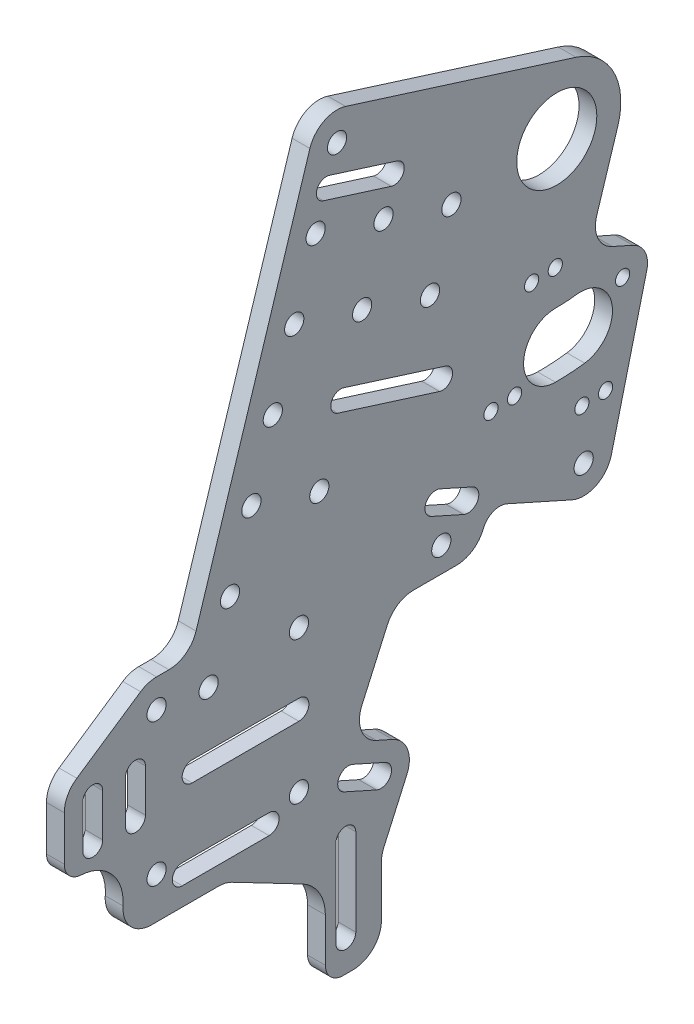
SolidWorks part; units mm, degrees
material "5052-H32"
ref_plane "Front Plane" through (0, 0, 0) normal (0, 0, 1) x (1, 0, 0)
ref_plane "Top Plane" through (0, 0, 0) normal (0, 1, 0) x (1, 0, 0)
ref_plane "Right Plane" through (0, 0, 0) normal (1, 0, 0) x (0, 0, -1)
sketch "Sketch2" plane through (0, 0, 0) normal (1, 0, 0) x (0, 0, -1)
  line L3 (55, 0) -> (-55, 0) construction
  line L9 (71.6952, 111.2048) -> (68.2175, 112.7608) construction
  line L28 (0, 0) -> (-57.2178, 40.0643) construction
  line L40 (0, 0) -> (113.3671, 198.5091) construction
  line L41 (113.3671, 198.5091) -> (58.7631, 215.7257) construction
  line L42 (99.338, 182.3162) -> (24.13, 14.224) construction
  line L44 (30.078, 221.0415) -> (54.3024, 213.4035)
  line L45 (32.2166, 227.8243) -> (56.441, 220.1864)
  line L49 (104.399, 158.5001) -> (136.8581, 143.9772) construction
  line L50 (136.8581, 143.9772) -> (122.3352, 111.518) construction
  line L51 (112.8406, 159.0638) -> (145.2997, 144.5408) construction
  line L56 (43.9148, 180.4584) -> (36.2769, 156.2339) construction
  line L57 (-29.4365, 93.5262) -> (-29.4365, 42.7262) construction
  line L61 (122.3352, 111.518) -> (89.876, 126.041) construction
  line L62 (89.876, 126.041) -> (104.399, 158.5001) construction
  line L63 (104.399, 158.5001) -> (122.3352, 111.518) construction
  line L65 (145.2997, 144.5408) -> (130.7768, 112.0817) construction
  line L66 (130.7768, 112.0817) -> (98.3176, 126.6046) construction
  line L67 (98.3176, 126.6046) -> (112.8406, 159.0638) construction
  line L68 (112.8406, 159.0638) -> (130.7768, 112.0817) construction
  line L69 (58.7631, 215.7257) -> (31.1473, 224.4329) construction
  line L70 (40.5747, 41.6494) -> (37.0969, 43.2054) construction
  line L71 (38.1, 20.2565) -> (38.1, -10.7315) construction
  line L72 (41.656, 20.2565) -> (41.656, -10.7315)
  line L73 (34.544, 20.2565) -> (34.544, -10.7315)
  line L74 (0, -14.2875) -> (38.1, -14.2875) construction
  line L75 (-20.2565, 38.1) -> (10.7315, 38.1) construction
  line L76 (-20.2565, 41.656) -> (10.7315, 41.656)
  line L77 (-20.2565, 34.544) -> (10.7315, 34.544)
  line L78 (14.2875, 38.1) -> (14.2875, 0) construction
  line L79 (-52.2013, 78.1643) -> (-52.2013, 62.9243) construction
  line L80 (-48.6453, 78.1643) -> (-48.6453, 62.9243)
  line L81 (-55.7573, 78.1643) -> (-55.7573, 62.9243)
  line L82 (-36.9613, 78.1643) -> (-36.9613, 62.9243) construction
  line L83 (-33.4053, 78.1643) -> (-33.4053, 62.9243)
  line L84 (-40.5173, 78.1643) -> (-40.5173, 62.9243)
  line L85 (31.1473, 224.4329) -> (-10.8613, 91.1986) construction
  line L86 (31.1473, 224.4329) -> (34.9663, 236.5451) construction
  line L92 (27.3284, 212.3207) -> (75.7772, 197.0448) construction
  line L93 (19.6904, 188.0963) -> (68.1392, 172.8204) construction
  line L94 (36.2769, 156.2339) -> (12.0525, 163.8719) construction
  line L95 (36.2769, 156.2339) -> (72.6135, 144.777) construction
  line L96 (37.3462, 159.6254) -> (73.6828, 148.1685)
  line L97 (35.2076, 152.8425) -> (71.5442, 141.3856)
  line L98 (36.2769, 156.2339) -> (28.639, 132.0095) construction
  line L99 (28.639, 132.0095) -> (4.4146, 139.6475) construction
  line L100 (-29.4365, 68.1262) -> (-16.7365, 68.1262) construction
  line L101 (-16.7365, 68.1262) -> (21.3635, 68.1262) construction
  line L102 (-16.7365, 71.6822) -> (21.3635, 71.6822)
  line L103 (-16.7365, 64.5702) -> (21.3635, 64.5702)
  line L104 (38.0214, 246.2349) -> (120.2412, 220.3111)
  line L105 (25.2765, 239.6003) -> (-15.3369, 110.7911)
  line L106 (-29.4365, 103.6862) -> (-25.0266, 103.6862)
  line L107 (-35.1197, 101.9481) -> (-57.8844, 86.5862)
  line L108 (-62.3613, 62.2565) -> (-62.3613, 78.1643)
  line L109 (-31.257, 27.94) -> (-7.2528, 27.94)
  line L110 (30.7975, -15.5575) -> (30.7975, 0)
  line L113 (135.1691, 191.635) -> (127.6222, 167.6992)
  line L114 (133.1625, 155.37) -> (140.4889, 152.092)
  line L115 (145.4838, 141.8254) -> (132.8214, 91.067)
  line L116 (118.8141, 84.2522) -> (95.6442, 94.6189)
  line L117 (50.8, 6.3603) -> (50.8, -11.7475)
  line L118 (37.1475, -21.9075) -> (40.64, -21.9075)
  line L120 (54.7606, 42.2589) -> (48.9643, 44.8523)
  line L121 (52.9447, 78.6256) -> (43.8397, 58.2757)
  line L122 (59.8853, 28.8354) -> (51.6859, 10.5098)
  line L123 (62.2187, 84.6362) -> (77.6364, 84.6362)
  line L124 (87.2546, 91.416) -> (86.9104, 90.6468)
  line L125 (30.7975, 0) -> (15.3035, 0) construction
  line L126 (22.4684, 13.7378) -> (-2.5545, 26.7884)
  line L127 (0, 0) -> (0, 15.494) construction
  line L128 (39.0186, 38.1716) -> (50.6112, 32.9849) construction
  line L129 (70.1392, 107.727) -> (81.7318, 102.5402) construction
  line L131 (71.6952, 111.2048) -> (83.2878, 106.018)
  line L132 (68.5832, 104.2492) -> (80.1757, 99.0625)
  line L133 (40.5747, 41.6494) -> (52.1672, 36.4626)
  line L134 (37.4626, 34.6938) -> (49.0552, 29.5071)
  circle A36 centre (0, 0) radius 14.2875 construction
  circle A37 centre (-57.2178, 40.0643) radius 14.2875 construction
  circle A38 centre (113.3671, 198.5091) radius 14.2875
  arc A39 (54.3024, 213.4035) -> (56.441, 220.1864) centre (55.3717, 216.795) ccw
  arc A40 (32.2166, 227.8243) -> (30.078, 221.0415) centre (31.1473, 224.4329) ccw
  circle A49 centre (-29.4365, 42.7262) radius 3.429
  circle A50 centre (21.3635, 93.5262) radius 3.429
  circle A51 centre (122.9635, 93.5262) radius 3.429
  circle A54 centre (104.399, 158.5001) radius 2.54
  circle A55 centre (136.8581, 143.9772) radius 2.54
  circle A56 centre (122.3352, 111.518) radius 2.54
  circle A57 centre (89.876, 126.041) radius 2.54
  arc A60 (113.3671, 135.0091) -> (121.8087, 135.5727) centre (113.3671, 198.5091) ccw construction
  circle A61 centre (112.8406, 159.0638) radius 2.54
  circle A62 centre (130.7768, 112.0817) radius 2.54
  circle A63 centre (98.3176, 126.6046) radius 2.54
  circle A64 centre (-29.4365, 93.5262) radius 3.429
  circle A65 centre (21.3635, 42.7262) radius 3.429
  circle A66 centre (72.1635, 93.5262) radius 3.429
  arc A67 (41.656, 20.2565) -> (34.544, 20.2565) centre (38.1, 20.2565) ccw
  arc A68 (34.544, -10.7315) -> (41.656, -10.7315) centre (38.1, -10.7315) ccw
  arc A69 (-20.2565, 41.656) -> (-20.2565, 34.544) centre (-20.2565, 38.1) ccw
  arc A70 (10.7315, 34.544) -> (10.7315, 41.656) centre (10.7315, 38.1) ccw
  arc A71 (-48.6453, 78.1643) -> (-55.7573, 78.1643) centre (-52.2013, 78.1643) ccw
  arc A72 (-55.7573, 62.9243) -> (-48.6453, 62.9243) centre (-52.2013, 62.9243) ccw
  arc A73 (-33.4053, 78.1643) -> (-40.5173, 78.1643) centre (-36.9613, 78.1643) ccw
  arc A74 (-40.5173, 62.9243) -> (-33.4053, 62.9243) centre (-36.9613, 62.9243) ccw
  circle A75 centre (34.9663, 236.5451) radius 3.429
  circle A76 centre (27.3284, 212.3207) radius 3.429
  circle A77 centre (19.6904, 188.0963) radius 3.429
  circle A78 centre (12.0525, 163.8719) radius 3.429
  circle A79 centre (4.4146, 139.6475) radius 3.429
  circle A80 centre (-3.2234, 115.423) radius 3.429
  circle A81 centre (-10.8613, 91.1986) radius 3.429
  circle A82 centre (51.5528, 204.6828) radius 3.429
  circle A83 centre (43.9148, 180.4584) radius 3.429
  circle A84 centre (75.7772, 197.0448) radius 3.429
  circle A85 centre (68.1392, 172.8204) radius 3.429
  arc A86 (37.3462, 159.6254) -> (35.2076, 152.8425) centre (36.2769, 156.2339) ccw
  arc A87 (71.5442, 141.3856) -> (73.6828, 148.1685) centre (72.6135, 144.777) ccw
  circle A88 centre (28.639, 132.0095) radius 3.429
  arc A89 (-16.7365, 71.6822) -> (-16.7365, 64.5702) centre (-16.7365, 68.1262) ccw
  arc A90 (21.3635, 64.5702) -> (21.3635, 71.6822) centre (21.3635, 68.1262) ccw
  arc A91 (38.0214, 246.2349) -> (25.2765, 239.6003) centre (34.9663, 236.5451) ccw
  arc A92 (120.2412, 220.3111) -> (135.1691, 191.635) centre (113.3671, 198.5091) cw
  arc A93 (-35.1197, 101.9481) -> (-29.4365, 103.6862) centre (-29.4365, 93.5262) cw
  arc A94 (-62.3613, 78.1643) -> (-57.8844, 86.5862) centre (-52.2013, 78.1643) cw
  arc A95 (-25.0266, 103.6862) -> (-15.3369, 110.7911) centre (-25.0266, 113.8462) ccw
  arc A96 (-56.356, 55.9159) -> (-62.3613, 62.2565) centre (-56.0113, 62.2565) cw
  arc A97 (-41.388, 38.8666) -> (-56.356, 55.9159) centre (-57.2178, 40.0643) ccw
  arc A99 (-31.257, 27.94) -> (-41.388, 38.8666) centre (-31.257, 38.1) cw
  arc A100 (37.1475, -21.9075) -> (30.7975, -15.5575) centre (37.1475, -15.5575) cw
  arc A101 (140.4889, 152.092) -> (145.4838, 141.8254) centre (136.8581, 143.9772) cw
  arc A102 (132.8214, 91.067) -> (118.8141, 84.2522) centre (122.9635, 93.5262) cw
  arc A105 (133.1625, 155.37) -> (127.6222, 167.6992) centre (137.3119, 164.644) cw
  arc A106 (121.8087, 135.5727) -> (112.9541, 135.0104) centre (113.3671, 198.5091) cw construction
  arc A107 (112.8797, 123.5807) -> (123.3282, 124.2442) centre (113.3671, 198.5091) ccw
  arc A108 (113.0284, 146.4402) -> (120.2892, 146.9013) centre (113.3671, 198.5091) ccw
  arc A109 (113.0284, 146.4402) -> (112.8797, 123.5807) centre (112.9541, 135.0104) ccw
  arc A110 (123.3282, 124.2442) -> (120.2892, 146.9013) centre (121.8087, 135.5727) ccw
  arc A111 (40.64, -21.9075) -> (50.8, -11.7475) centre (40.64, -11.7475) ccw
  arc A112 (50.8, 6.3603) -> (51.6859, 10.5098) centre (60.96, 6.3603) cw
  arc A113 (54.7606, 42.2589) -> (59.8853, 28.8354) centre (50.6112, 32.9849) cw
  arc A114 (48.9643, 44.8523) -> (43.8397, 58.2757) centre (53.1137, 54.1263) cw
  arc A115 (62.2187, 84.6362) -> (52.9447, 78.6256) centre (62.2187, 74.4762) ccw
  arc A117 (77.6364, 84.6362) -> (86.9104, 90.6468) centre (77.6364, 94.7962) ccw
  arc A118 (87.2546, 91.416) -> (95.6442, 94.6189) centre (93.0509, 88.8226) cw
  arc A121 (30.7975, 0) -> (22.4684, 13.7378) centre (15.3035, 0) ccw
  arc A122 (-7.2528, 27.94) -> (-2.5545, 26.7884) centre (-7.2528, 17.78) cw
  arc A126 (71.6952, 111.2048) -> (68.5832, 104.2492) centre (70.1392, 107.727) ccw
  arc A127 (80.1757, 99.0625) -> (83.2878, 106.018) centre (81.7318, 102.5402) ccw
  arc A128 (40.5747, 41.6494) -> (37.4626, 34.6938) centre (39.0186, 38.1716) ccw
  arc A129 (49.0552, 29.5071) -> (52.1672, 36.4626) centre (50.6112, 32.9849) ccw
  point P26 (66.6614, 109.283)
  point P31 (113.3671, 135.0091)
  point P37 (2.3135, 68.1262)
  point P38 (35.5409, 39.7276)
  point P40 (75.9355, 105.1336)
  point P43 (44.8149, 35.5782)
  point P70 (54.4452, 150.5055)
  point P80 (121.8087, 135.5727)
  point P89 (38.1, 4.7625)
  point P98 (-4.7625, 38.1)
  point P100 (38.1, 23.8125)
  point P109 (-23.8125, 38.1)
  point P111 (-52.2013, 70.5443)
  point P116 (-36.9613, 70.5443)
  point P176 (117.3912, 135.1367)
  point P179 (-4.7625, 27.94)
  point P201 (64.0347, 38.1095)
  point P204 (39.6903, 49.0017)
  dimension "D1" = 28.575
  dimension "D2" = 69.85
  dimension "D5" = 25.4
  dimension "D6" = 3.556
  dimension "D7" = 184.15
  dimension "D8" = 28.0103
  dimension "D9" = 7.62
  dimension "D10" = 10.16
  dimension "D11" = 27.7812
  dimension "D13" = 6.858
  dimension "D15" = 53.4619
  dimension "D17" = 180.1812
  dimension "D18" = 53.4619
  dimension "D19" = 3.556
  dimension "D20" = 38.1
  dimension "D21" = 38.1
  dimension "D24" = 5.08
  dimension "D28" = 10.16
  dimension "D30" = 35.56
  dimension "D31" = 8.4416
  dimension "D33" = 65.895
  dimension "D34" = 35
  dimension "D35" = 60.27
  dimension "D40" = 76.2
  dimension "D16" = 7.62
  dimension "D27" = 10.16
  dimension "D47" = 38.1
  dimension "D48" = 7.112
  dimension "D50" = 38.1
  dimension "D53" = 3.556
  dimension "D56" = 12.7
  dimension "D57" = 12.7
  dimension "D58" = 25.4
  dimension "D60" = 25.4
  dimension "D61" = 25.4
  dimension "D25" = 3.556
  dimension "D63" = 6.35
  dimension "D64" = 31.75
  dimension "D65" = 10.16
  dimension "D69" = 16.51
  dimension "D70" = 12.7
  dimension "D73" = 6.35
  dimension "D74" = 8.89
  dimension "D72" = 8.89
  dimension "D75" = 11.43
  dimension "D77" = 7.2813
  dimension "D78" = 15.494
  dimension "D81" = 15.494
  dimension "D82" = 10.16
  dimension "D83" = 6.35
  dimension "D38" = 17.7847
  dimension "D3" = 228.6
  dimension "D12" = 2.6619
  dimension "D14" = 78.5812
  dimension "D22" = 35.56
  dimension "D23" = 63.5
  dimension "D26" = 12.7
  dimension "D29" = 8.4667
  dimension "D32" = 50.8
  dimension "D36" = 16.1929
  dimension "D37" = 12.7
  dimension "D39" = 76.2
  dimension "D41" = 12.7
  dimension "D43" = 17.5
  dimension "D44" = 7.112
  dimension "D45" = 3.556
  dimension "D46" = 38.1
  dimension "D49" = 38.1
  dimension "D51" = 15.24
  dimension "D52" = 15.24
  dimension "D54" = 38.1
  dimension "D55" = 23.8125
  dimension "D59" = 25.4
  dimension "D62" = 25.4
  dimension "D66" = 15.494
  dimension "D67" = 3
  dimension "D68" = 25.4
  dimension "D71" = 7.62
  dimension "D76" = 60.8098
extrude "Boss-Extrude1" add sketch "Sketch2" along normal blind 3.175 and the other way blind 3.175
sketch "Sketch3" plane through (3.175, 0, 0) normal (1, 0, 0) x (0, 0, -1)
  text T0 "3597" font "A4 SPEED" height 11.43
  dimension "D1" = 106.68
  dimension "D2" = 5.08
extrude "Cut-Extrude1" [suppressed] cut sketch "Sketch3" against normal through all
